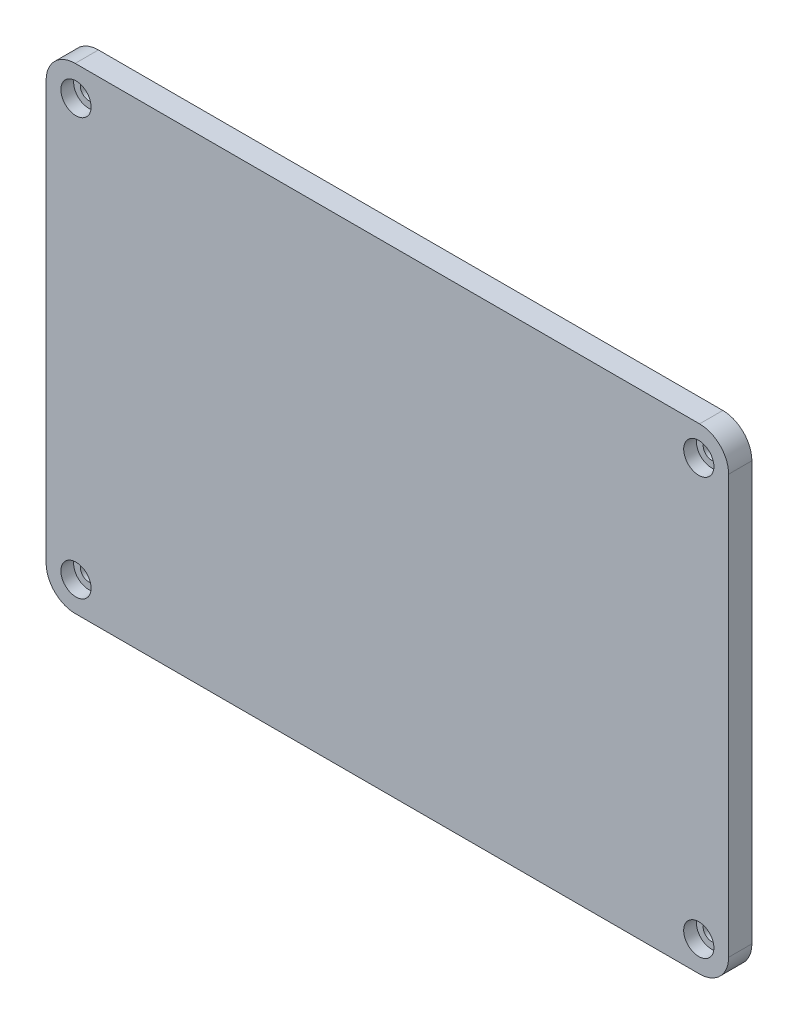
SolidWorks part; units mm, degrees
ref_plane "Front Plane" through (0, 0, 0) normal (0, 0, 1) x (1, 0, 0)
ref_plane "Top Plane" through (0, 0, 0) normal (0, 1, 0) x (1, 0, 0)
ref_plane "Right Plane" through (0, 0, 0) normal (1, 0, 0) x (0, 0, -1)
sketch "Sketch1" plane through (0, 0, 0) normal (0, 0, 1) x (1, 0, 0)
  line L0 (-700.5296, 908.6614) -> (-593.0698, 908.6614)
  line L1 (-588.0698, 903.6614) -> (-588.0698, 831.66)
  line L2 (-700.5296, 826.66) -> (-593.0698, 826.66)
  line L3 (-705.5296, 831.66) -> (-705.5296, 903.6614)
  arc A0 (-700.5296, 908.6614) -> (-705.5296, 903.6614) centre (-700.5296, 903.6614) ccw
  arc A1 (-593.0698, 908.6614) -> (-588.0698, 903.6614) centre (-593.0698, 903.6614) cw
  arc A2 (-588.0698, 831.66) -> (-593.0698, 826.66) centre (-593.0698, 831.66) cw
  arc A3 (-705.5296, 831.66) -> (-700.5296, 826.66) centre (-700.5296, 831.66) ccw
extrude "Boss-Extrude1" add sketch "Sketch1" along normal blind 4
sketch "Sketch2" plane through (0, 0, 4) normal (0, 0, 1) x (1, 0, 0)
  point P0 (-700.3935, 903.5254)
  point P1 (-593.2058, 903.5254)
  point P3 (-593.2058, 831.796)
  point P5 (-700.3935, 831.796)
hole_wizard "CBORE for M5 Hex Head Bolt1" positions "Sketch2" profile "Sketch3" counterbore size "M5" standard "ANSI Metric" end condition up to next
sketch "Sketch3" plane through (-700.3935, 903.5254, 4) normal (1, 0, 0) x (0, -1, 0)
  line L0 (0, 0) -> (0, 4)
  line L1 (0, 4) -> (1.45, 4)
  line L3 (1.45, 4) -> (1.45, 2.2)
  line L4 (1.45, 2.2) -> (2.6, 2.2)
  line L5 (2.6, 2.2) -> (2.6, 0)
  line L7 (2.6, 0) -> (0, 0)
  line L11 (0, -6.35) -> (0, 107.95) construction
  dimension "Thru Hole Dia." = 2.9
  dimension "Thru Hole Depth" = 4
  dimension "C'Bore Dia." = 5.2
  dimension "C'Bore Depth" = 2.2
